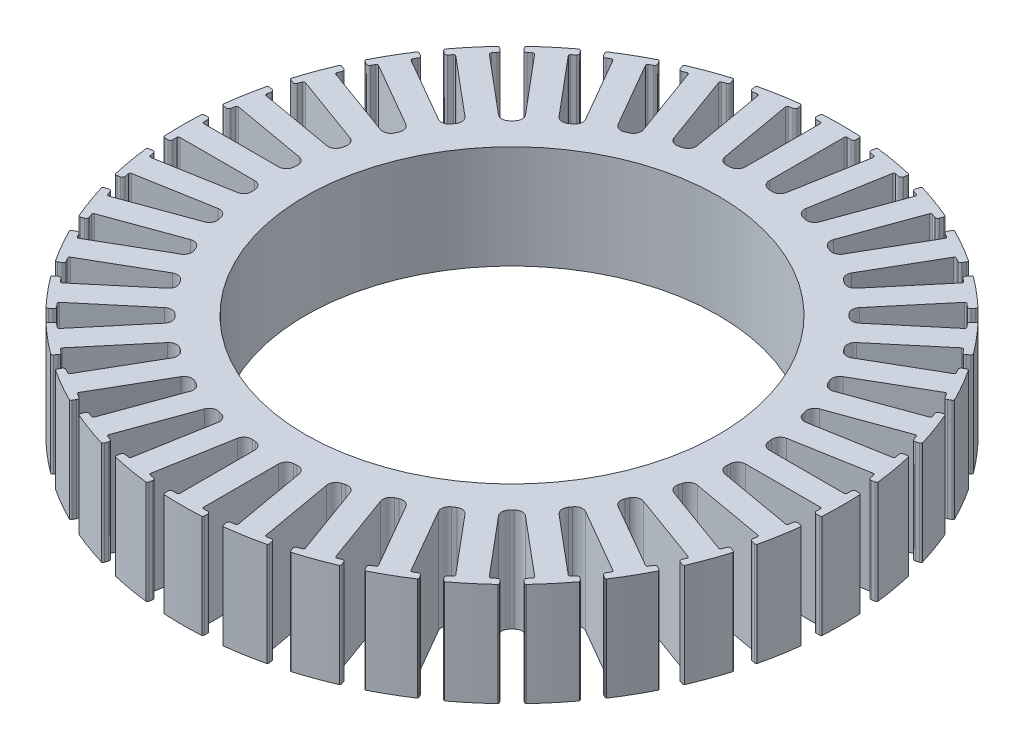
SolidWorks part; units mm, degrees
material "1023 Carbon Steel Sheet (SS)"
ref_plane "Front Plane" through (0, 0, 0) normal (0, 0, 1) x (1, 0, 0)
ref_plane "Top Plane" through (0, 0, 0) normal (0, 1, 0) x (1, 0, 0)
ref_plane "Right Plane" through (0, 0, 0) normal (1, 0, 0) x (0, 0, -1)
sketch "Sketch1" plane through (0, 0, 0) normal (0, 1, 0) x (1, 0, 0)
  line L0 (0, 0) -> (26, 0) construction
  line L1 (40.5, -1.7) -> (40.5, -2.2)
  line L2 (41.5, 1.5) -> (41.4729, 1.5)
  line L3 (41.5, 1.5) -> (41.5, -1.5)
  line L4 (41.5, -1.5) -> (41.4729, -1.5)
  line L6 (41.2, 2.5) -> (40.8, 2.5)
  line L7 (41.5, 2.2) -> (41.5, -2.2)
  line L8 (41.2, -2.5) -> (40.8, -2.5)
  line L9 (40.5, 2.2) -> (40.5, 1.7)
  line L10 (40.3, 1.5) -> (30.899, 1.5)
  line L11 (40.3, -1.5) -> (30.899, -1.5)
  line L12 (39.9482, -5.5208) -> (30.6901, -3.8883)
  line L13 (39.4273, -8.4752) -> (30.1691, -6.8428)
  line L14 (41.0082, -4.6923) -> (40.6143, -4.6228)
  line L15 (41.2515, -5.0398) -> (40.4875, -9.373)
  line L16 (40.2667, -4.8662) -> (40.1799, -5.3586)
  line L17 (39.5895, -8.7069) -> (39.5027, -9.1993)
  line L18 (40.14, -9.6163) -> (39.746, -9.5469)
  line L19 (38.3826, -12.3739) -> (29.5486, -9.1586)
  line L20 (37.3566, -15.193) -> (28.5226, -11.9776)
  line L21 (39.5704, -11.742) -> (39.1945, -11.6052)
  line L22 (39.7497, -12.1265) -> (38.2448, -16.2612)
  line L23 (38.81, -11.7845) -> (38.639, -12.2543)
  line L24 (37.4761, -15.4493) -> (37.3051, -15.9191)
  line L25 (37.8603, -16.4405) -> (37.4844, -16.3037)
  line L26 (35.6508, -18.851) -> (27.5093, -14.1505)
  line L27 (34.1508, -21.449) -> (26.0093, -16.7486)
  line L28 (36.9302, -18.4349) -> (36.5838, -18.2349)
  line L29 (37.0401, -18.8447) -> (34.8401, -22.6553)
  line L30 (36.174, -18.3447) -> (35.924, -18.7778)
  line L31 (34.224, -21.7222) -> (33.974, -22.1553)
  line L32 (34.4302, -22.7651) -> (34.0838, -22.5651)
  line L33 (31.8358, -24.7553) -> (24.6342, -18.7124)
  line L34 (29.9074, -27.0534) -> (22.7058, -21.0106)
  line L35 (33.168, -24.5677) -> (32.8616, -24.3106)
  line L36 (33.205, -24.9904) -> (30.3767, -28.361)
  line L37 (32.4389, -24.3476) -> (32.1175, -24.7306)
  line L38 (29.9321, -27.3352) -> (29.6107, -27.7182)
  line L39 (29.9541, -28.398) -> (29.6476, -28.1408)
  line L40 (27.0534, -29.9074) -> (21.0106, -22.7058)
  line L41 (24.7553, -31.8358) -> (18.7124, -24.6342)
  line L42 (28.398, -29.9541) -> (28.1408, -29.6476)
  line L43 (28.361, -30.3767) -> (24.9904, -33.205)
  line L44 (27.7182, -29.6107) -> (27.3352, -29.9321)
  line L45 (24.7306, -32.1175) -> (24.3476, -32.4389)
  line L46 (24.5677, -33.168) -> (24.3106, -32.8616)
  line L47 (21.449, -34.1508) -> (16.7486, -26.0093)
  line L48 (18.851, -35.6508) -> (14.1505, -27.5093)
  line L49 (22.7651, -34.4302) -> (22.5651, -34.0838)
  line L50 (22.6553, -34.8401) -> (18.8447, -37.0401)
  line L51 (22.1553, -33.974) -> (21.7222, -34.224)
  line L52 (18.7778, -35.924) -> (18.3447, -36.174)
  line L53 (18.4349, -36.9302) -> (18.2349, -36.5838)
  line L54 (11.9776, -28.5226) -> (15.193, -37.3566)
  line L55 (12.3739, -38.3826) -> (9.1586, -29.5486)
  line L56 (16.4405, -37.8603) -> (16.3037, -37.4844)
  line L57 (16.2612, -38.2448) -> (12.1265, -39.7497)
  line L58 (15.9191, -37.3051) -> (15.4493, -37.4761)
  line L59 (12.2543, -38.639) -> (11.7845, -38.81)
  line L60 (11.742, -39.5704) -> (11.6052, -39.1945)
  line L61 (8.4752, -39.4273) -> (6.8428, -30.1691)
  line L62 (5.5208, -39.9482) -> (3.8883, -30.6901)
  line L63 (9.6163, -40.14) -> (9.5469, -39.746)
  line L64 (9.373, -40.4875) -> (5.0398, -41.2515)
  line L65 (9.1993, -39.5027) -> (8.7069, -39.5895)
  line L66 (5.3586, -40.1799) -> (4.8662, -40.2667)
  line L67 (4.6923, -41.0082) -> (4.6228, -40.6143)
  line L68 (1.5, -40.3) -> (1.5, -30.899)
  line L69 (-1.5, -40.3) -> (-1.5, -30.899)
  line L70 (2.5, -41.2) -> (2.5, -40.8)
  line L71 (2.2, -41.5) -> (-2.2, -41.5)
  line L72 (2.2, -40.5) -> (1.7, -40.5)
  line L73 (-1.7, -40.5) -> (-2.2, -40.5)
  line L74 (-2.5, -41.2) -> (-2.5, -40.8)
  line L75 (-5.5208, -39.9482) -> (-3.8883, -30.6901)
  line L76 (-8.4752, -39.4273) -> (-6.8428, -30.1691)
  line L77 (-4.6923, -41.0082) -> (-4.6228, -40.6143)
  line L78 (-5.0398, -41.2515) -> (-9.373, -40.4875)
  line L79 (-4.8662, -40.2667) -> (-5.3586, -40.1799)
  line L80 (-8.7069, -39.5895) -> (-9.1993, -39.5027)
  line L81 (-9.6163, -40.14) -> (-9.5469, -39.746)
  line L82 (-12.3739, -38.3826) -> (-9.1586, -29.5486)
  line L83 (-15.193, -37.3566) -> (-11.9776, -28.5226)
  line L84 (-11.742, -39.5704) -> (-11.6052, -39.1945)
  line L85 (-12.1265, -39.7497) -> (-16.2612, -38.2448)
  line L86 (-11.7845, -38.81) -> (-12.2543, -38.639)
  line L87 (-15.4493, -37.4761) -> (-15.9191, -37.3051)
  line L88 (-16.4405, -37.8603) -> (-16.3037, -37.4844)
  line L89 (-18.851, -35.6508) -> (-14.1505, -27.5093)
  line L90 (-21.449, -34.1508) -> (-16.7486, -26.0093)
  line L91 (-18.4349, -36.9302) -> (-18.2349, -36.5838)
  line L92 (-18.8447, -37.0401) -> (-22.6553, -34.8401)
  line L93 (-18.3447, -36.174) -> (-18.7778, -35.924)
  line L94 (-21.7222, -34.224) -> (-22.1553, -33.974)
  line L95 (-22.7651, -34.4302) -> (-22.5651, -34.0838)
  line L96 (-24.7553, -31.8358) -> (-18.7124, -24.6342)
  line L97 (-27.0534, -29.9074) -> (-21.0106, -22.7058)
  line L98 (-24.5677, -33.168) -> (-24.3106, -32.8616)
  line L99 (-24.9904, -33.205) -> (-28.361, -30.3767)
  line L100 (-24.3476, -32.4389) -> (-24.7306, -32.1175)
  line L101 (-27.3352, -29.9321) -> (-27.7182, -29.6107)
  line L102 (-28.398, -29.9541) -> (-28.1408, -29.6476)
  line L103 (-29.9074, -27.0534) -> (-22.7058, -21.0106)
  line L104 (-31.8358, -24.7553) -> (-24.6342, -18.7124)
  line L105 (-29.9541, -28.398) -> (-29.6476, -28.1408)
  line L106 (-30.3767, -28.361) -> (-33.205, -24.9904)
  line L107 (-29.6107, -27.7182) -> (-29.9321, -27.3352)
  line L108 (-32.1175, -24.7306) -> (-32.4389, -24.3476)
  line L109 (-33.168, -24.5677) -> (-32.8616, -24.3106)
  line L110 (-34.1508, -21.449) -> (-26.0093, -16.7486)
  line L111 (-35.6508, -18.851) -> (-27.5093, -14.1505)
  line L112 (-34.4302, -22.7651) -> (-34.0838, -22.5651)
  line L113 (-34.8401, -22.6553) -> (-37.0401, -18.8447)
  line L114 (-33.974, -22.1553) -> (-34.224, -21.7222)
  line L115 (-35.924, -18.7778) -> (-36.174, -18.3447)
  line L116 (-36.9302, -18.4349) -> (-36.5838, -18.2349)
  line L117 (-37.3566, -15.193) -> (-28.5226, -11.9776)
  line L118 (-38.3826, -12.3739) -> (-29.5486, -9.1586)
  line L119 (-37.8603, -16.4405) -> (-37.4844, -16.3037)
  line L120 (-38.2448, -16.2612) -> (-39.7497, -12.1265)
  line L121 (-37.3051, -15.9191) -> (-37.4761, -15.4493)
  line L122 (-38.639, -12.2543) -> (-38.81, -11.7845)
  line L123 (-39.5704, -11.742) -> (-39.1945, -11.6052)
  line L124 (-39.4273, -8.4752) -> (-30.1691, -6.8428)
  line L125 (-39.9482, -5.5208) -> (-30.6901, -3.8883)
  line L126 (-40.14, -9.6163) -> (-39.746, -9.5469)
  line L127 (-40.4875, -9.373) -> (-41.2515, -5.0398)
  line L128 (-39.5027, -9.1993) -> (-39.5895, -8.7069)
  line L129 (-40.1799, -5.3586) -> (-40.2667, -4.8662)
  line L130 (-41.0082, -4.6923) -> (-40.6143, -4.6228)
  line L131 (-40.3, -1.5) -> (-30.899, -1.5)
  line L132 (-40.3, 1.5) -> (-30.899, 1.5)
  line L133 (-41.2, -2.5) -> (-40.8, -2.5)
  line L134 (-41.5, -2.2) -> (-41.5, 2.2)
  line L135 (-40.5, -2.2) -> (-40.5, -1.7)
  line L136 (-40.5, 1.7) -> (-40.5, 2.2)
  line L137 (-41.2, 2.5) -> (-40.8, 2.5)
  line L138 (-39.9482, 5.5208) -> (-30.6901, 3.8883)
  line L139 (-39.4273, 8.4752) -> (-30.1691, 6.8428)
  line L140 (-41.0082, 4.6923) -> (-40.6143, 4.6228)
  line L141 (-41.2515, 5.0398) -> (-40.4875, 9.373)
  line L142 (-40.2667, 4.8662) -> (-40.1799, 5.3586)
  line L143 (-39.5895, 8.7069) -> (-39.5027, 9.1993)
  line L144 (-40.14, 9.6163) -> (-39.746, 9.5469)
  line L145 (-38.3826, 12.3739) -> (-29.5486, 9.1586)
  line L146 (-37.3566, 15.193) -> (-28.5226, 11.9776)
  line L147 (-39.5704, 11.742) -> (-39.1945, 11.6052)
  line L148 (-39.7497, 12.1265) -> (-38.2448, 16.2612)
  line L149 (-38.81, 11.7845) -> (-38.639, 12.2543)
  line L150 (-37.4761, 15.4493) -> (-37.3051, 15.9191)
  line L151 (-37.8603, 16.4405) -> (-37.4844, 16.3037)
  line L152 (-35.6508, 18.851) -> (-27.5093, 14.1505)
  line L153 (-34.1508, 21.449) -> (-26.0093, 16.7486)
  line L154 (-36.9302, 18.4349) -> (-36.5838, 18.2349)
  line L155 (-37.0401, 18.8447) -> (-34.8401, 22.6553)
  line L156 (-36.174, 18.3447) -> (-35.924, 18.7778)
  line L157 (-34.224, 21.7222) -> (-33.974, 22.1553)
  line L158 (-34.4302, 22.7651) -> (-34.0838, 22.5651)
  line L159 (-31.8358, 24.7553) -> (-24.6342, 18.7124)
  line L160 (-29.9074, 27.0534) -> (-22.7058, 21.0106)
  line L161 (-33.168, 24.5677) -> (-32.8616, 24.3106)
  line L162 (-33.205, 24.9904) -> (-30.3767, 28.361)
  line L163 (-32.4389, 24.3476) -> (-32.1175, 24.7306)
  line L164 (-29.9321, 27.3352) -> (-29.6107, 27.7182)
  line L165 (-29.9541, 28.398) -> (-29.6476, 28.1408)
  line L166 (-27.0534, 29.9074) -> (-21.0106, 22.7058)
  line L167 (-24.7553, 31.8358) -> (-18.7124, 24.6342)
  line L168 (-28.398, 29.9541) -> (-28.1408, 29.6476)
  line L169 (-28.361, 30.3767) -> (-24.9904, 33.205)
  line L170 (-27.7182, 29.6107) -> (-27.3352, 29.9321)
  line L171 (-24.7306, 32.1175) -> (-24.3476, 32.4389)
  line L172 (-24.5677, 33.168) -> (-24.3106, 32.8616)
  line L173 (-21.449, 34.1508) -> (-16.7486, 26.0093)
  line L174 (-18.851, 35.6508) -> (-14.1505, 27.5093)
  line L175 (-22.7651, 34.4302) -> (-22.5651, 34.0838)
  line L176 (-22.6553, 34.8401) -> (-18.8447, 37.0401)
  line L177 (-22.1553, 33.974) -> (-21.7222, 34.224)
  line L178 (-18.7778, 35.924) -> (-18.3447, 36.174)
  line L179 (-18.4349, 36.9302) -> (-18.2349, 36.5838)
  line L180 (-15.193, 37.3566) -> (-11.9776, 28.5226)
  line L181 (-12.3739, 38.3826) -> (-9.1586, 29.5486)
  line L182 (-16.4405, 37.8603) -> (-16.3037, 37.4844)
  line L183 (-16.2612, 38.2448) -> (-12.1265, 39.7497)
  line L184 (-15.9191, 37.3051) -> (-15.4493, 37.4761)
  line L185 (-12.2543, 38.639) -> (-11.7845, 38.81)
  line L186 (-11.742, 39.5704) -> (-11.6052, 39.1945)
  line L187 (-8.4752, 39.4273) -> (-6.8428, 30.1691)
  line L188 (-5.5208, 39.9482) -> (-3.8883, 30.6901)
  line L189 (-9.6163, 40.14) -> (-9.5469, 39.746)
  line L190 (-9.373, 40.4875) -> (-5.0398, 41.2515)
  line L191 (-9.1993, 39.5027) -> (-8.7069, 39.5895)
  line L192 (-5.3586, 40.1799) -> (-4.8662, 40.2667)
  line L193 (-4.6923, 41.0082) -> (-4.6228, 40.6143)
  line L194 (-1.5, 40.3) -> (-1.5, 30.899)
  line L195 (1.5, 40.3) -> (1.5, 30.899)
  line L196 (-2.5, 41.2) -> (-2.5, 40.8)
  line L197 (-2.2, 41.5) -> (2.2, 41.5)
  line L198 (-2.2, 40.5) -> (-1.7, 40.5)
  line L199 (1.7, 40.5) -> (2.2, 40.5)
  line L200 (2.5, 41.2) -> (2.5, 40.8)
  line L201 (5.5208, 39.9482) -> (3.8883, 30.6901)
  line L202 (8.4752, 39.4273) -> (6.8428, 30.1691)
  line L203 (4.6923, 41.0082) -> (4.6228, 40.6143)
  line L204 (5.0398, 41.2515) -> (9.373, 40.4875)
  line L205 (4.8662, 40.2667) -> (5.3586, 40.1799)
  line L206 (8.7069, 39.5895) -> (9.1993, 39.5027)
  line L207 (9.6163, 40.14) -> (9.5469, 39.746)
  line L208 (12.3739, 38.3826) -> (9.1586, 29.5486)
  line L209 (15.193, 37.3566) -> (11.9776, 28.5226)
  line L210 (11.742, 39.5704) -> (11.6052, 39.1945)
  line L211 (12.1265, 39.7497) -> (16.2612, 38.2448)
  line L212 (11.7845, 38.81) -> (12.2543, 38.639)
  line L213 (15.4493, 37.4761) -> (15.9191, 37.3051)
  line L214 (16.4405, 37.8603) -> (16.3037, 37.4844)
  line L215 (18.851, 35.6508) -> (14.1505, 27.5093)
  line L216 (21.449, 34.1508) -> (16.7486, 26.0093)
  line L217 (18.4349, 36.9302) -> (18.2349, 36.5838)
  line L218 (18.8447, 37.0401) -> (22.6553, 34.8401)
  line L219 (18.3447, 36.174) -> (18.7778, 35.924)
  line L220 (21.7222, 34.224) -> (22.1553, 33.974)
  line L221 (22.7651, 34.4302) -> (22.5651, 34.0838)
  line L222 (24.7553, 31.8358) -> (18.7124, 24.6342)
  line L223 (27.0534, 29.9074) -> (21.0106, 22.7058)
  line L224 (24.5677, 33.168) -> (24.3106, 32.8616)
  line L225 (24.9904, 33.205) -> (28.361, 30.3767)
  line L226 (24.3476, 32.4389) -> (24.7306, 32.1175)
  line L227 (27.3352, 29.9321) -> (27.7182, 29.6107)
  line L228 (28.398, 29.9541) -> (28.1408, 29.6476)
  line L229 (29.9074, 27.0534) -> (22.7058, 21.0106)
  line L230 (31.8358, 24.7553) -> (24.6342, 18.7124)
  line L231 (29.9541, 28.398) -> (29.6476, 28.1408)
  line L232 (30.3767, 28.361) -> (33.205, 24.9904)
  line L233 (29.6107, 27.7182) -> (29.9321, 27.3352)
  line L234 (32.1175, 24.7306) -> (32.4389, 24.3476)
  line L235 (33.168, 24.5677) -> (32.8616, 24.3106)
  line L236 (34.1508, 21.449) -> (26.0093, 16.7486)
  line L237 (35.6508, 18.851) -> (27.5093, 14.1505)
  line L238 (34.4302, 22.7651) -> (34.0838, 22.5651)
  line L239 (34.8401, 22.6553) -> (37.0401, 18.8447)
  line L240 (33.974, 22.1553) -> (34.224, 21.7222)
  line L241 (35.924, 18.7778) -> (36.174, 18.3447)
  line L242 (36.9302, 18.4349) -> (36.5838, 18.2349)
  line L243 (37.3566, 15.193) -> (28.5226, 11.9776)
  line L244 (38.3826, 12.3739) -> (29.5486, 9.1586)
  line L245 (37.8603, 16.4405) -> (37.4844, 16.3037)
  line L246 (38.2448, 16.2612) -> (39.7497, 12.1265)
  line L247 (37.3051, 15.9191) -> (37.4761, 15.4493)
  line L248 (38.639, 12.2543) -> (38.81, 11.7845)
  line L249 (39.5704, 11.742) -> (39.1945, 11.6052)
  line L250 (39.4273, 8.4752) -> (30.1691, 6.8428)
  line L251 (39.9482, 5.5208) -> (30.6901, 3.8883)
  line L252 (40.14, 9.6163) -> (39.746, 9.5469)
  line L253 (40.4875, 9.373) -> (41.2515, 5.0398)
  line L254 (39.5027, 9.1993) -> (39.5895, 8.7069)
  line L255 (40.1799, 5.3586) -> (40.2667, 4.8662)
  line L256 (41.0082, 4.6923) -> (40.6143, 4.6228)
  line L257 (15.193, -37.3566) -> (11.9776, -28.5226) [skipped]
  line L258 (-7.5751, 29.0279) -> (-7.9537, 28.9291)
  line L259 (17.0464, -24.6865) -> (17.4841, -24.3842)
  circle A0 centre (0, 0) radius 41.5
  arc A1 (41.5, -2.2) -> (41.2, -2.5) centre (41.2, -2.2) cw
  arc A2 (40.8, -2.5) -> (40.5, -2.2) centre (40.8, -2.2) cw
  arc A3 (41.2, 2.5) -> (41.5, 2.2) centre (41.2, 2.2) cw
  arc A4 (40.8, 2.5) -> (40.5, 2.2) centre (40.8, 2.2) ccw
  arc A5 (40.5, -1.7) -> (40.3, -1.5) centre (40.3, -1.7) ccw
  arc A6 (40.5, 1.7) -> (40.3, 1.5) centre (40.3, 1.7) cw
  circle A7 centre (0, 0) radius 26
  arc A8 (29.9023, 2.4194) -> (29.8681, 2.8099) centre (0, 0) ccw
  arc A9 (30.899, -1.5) -> (29.9023, -2.4194) centre (30.899, -2.5) ccw
  arc A10 (30.899, 1.5) -> (29.9023, 2.4194) centre (30.899, 2.5) cw
  arc A11 (30.6901, -3.8883) -> (29.8681, -2.8099) centre (30.8637, -2.9035) cw
  arc A12 (30.1691, -6.8428) -> (29.0279, -7.5751) centre (29.9955, -7.8276) ccw
  arc A13 (41.0082, -4.6923) -> (41.2515, -5.0398) centre (40.9561, -4.9877) cw
  arc A14 (40.6143, -4.6228) -> (40.2667, -4.8662) centre (40.5622, -4.9183) ccw
  arc A15 (40.1799, -5.3586) -> (39.9482, -5.5208) centre (39.983, -5.3238) cw
  arc A16 (39.5895, -8.7069) -> (39.4273, -8.4752) centre (39.3926, -8.6722) ccw
  arc A17 (39.746, -9.5469) -> (39.5027, -9.1993) centre (39.7981, -9.2514) cw
  arc A18 (40.4875, -9.373) -> (40.14, -9.6163) centre (40.1921, -9.3209) cw
  arc A19 (29.5486, -9.1586) -> (28.9264, -7.9537) centre (29.8906, -8.2189) cw
  arc A20 (28.5226, -11.9776) -> (27.2715, -12.5006) centre (28.1805, -12.9173) ccw
  arc A21 (39.5704, -11.742) -> (39.7497, -12.1265) centre (39.4678, -12.0239) cw
  arc A22 (39.1945, -11.6052) -> (38.81, -11.7845) centre (39.0919, -11.8871) ccw
  arc A23 (38.639, -12.2543) -> (38.3826, -12.3739) centre (38.451, -12.1859) cw
  arc A24 (37.4761, -15.4493) -> (37.3566, -15.193) centre (37.2882, -15.3809) ccw
  arc A25 (37.4844, -16.3037) -> (37.3051, -15.9191) centre (37.587, -16.0217) cw
  arc A26 (38.2448, -16.2612) -> (37.8603, -16.4405) centre (37.9629, -16.1586) cw
  arc A27 (27.5093, -14.1505) -> (27.1058, -12.8559) centre (28.0093, -13.2845) cw
  arc A28 (26.0093, -16.7486) -> (24.6865, -17.0464) centre (25.5093, -17.6146) ccw
  arc A29 (36.9302, -18.4349) -> (37.0401, -18.8447) centre (36.7802, -18.6947) cw
  arc A30 (36.5838, -18.2349) -> (36.174, -18.3447) centre (36.4338, -18.4947) ccw
  arc A31 (35.924, -18.7778) -> (35.6508, -18.851) centre (35.7508, -18.6778) cw
  arc A32 (34.224, -21.7222) -> (34.1508, -21.449) centre (34.0508, -21.6222) ccw
  arc A33 (34.0838, -22.5651) -> (33.974, -22.1553) centre (34.2338, -22.3053) cw
  arc A34 (34.8401, -22.6553) -> (34.4302, -22.7651) centre (34.5802, -22.5053) cw
  arc A35 (24.6342, -18.7124) -> (24.4616, -17.3675) centre (25.277, -17.9464) cw
  arc A36 (22.7058, -21.0106) -> (21.3513, -21.0742) centre (22.0631, -21.7766) ccw
  arc A37 (33.168, -24.5677) -> (33.205, -24.9904) centre (32.9752, -24.7976) cw
  arc A38 (32.8616, -24.3106) -> (32.4389, -24.3476) centre (32.6687, -24.5404) ccw
  arc A39 (32.1175, -24.7306) -> (31.8358, -24.7553) centre (31.9643, -24.6021) cw
  arc A40 (29.9321, -27.3352) -> (29.9074, -27.0534) centre (29.7789, -27.2066) ccw
  arc A41 (29.6476, -28.1408) -> (29.6107, -27.7182) centre (29.8405, -27.911) cw
  arc A42 (30.3767, -28.361) -> (29.9541, -28.398) centre (30.1469, -28.1681) cw
  arc A43 (21.0106, -22.7058) -> (21.0742, -21.3513) centre (21.7766, -22.0631) cw
  arc A44 (-7.9537, 28.9291) -> (-9.1586, 29.5486) centre (-8.2197, 29.893) cw
  arc A45 (28.398, -29.9541) -> (28.361, -30.3767) centre (28.1681, -30.1469) cw
  arc A46 (28.1408, -29.6476) -> (27.7182, -29.6107) centre (27.911, -29.8405) ccw
  arc A47 (27.3352, -29.9321) -> (27.0534, -29.9074) centre (27.2066, -29.7789) cw
  arc A48 (24.7306, -32.1175) -> (24.7553, -31.8358) centre (24.6021, -31.9643) ccw
  arc A49 (24.3106, -32.8616) -> (24.3476, -32.4389) centre (24.5404, -32.6687) cw
  arc A50 (24.9904, -33.205) -> (24.5677, -33.168) centre (24.7976, -32.9752) cw
  arc A51 (16.7486, -26.0093) -> (17.0464, -24.6865) centre (17.6146, -25.5093) cw
  arc A52 (14.1505, -27.5093) -> (12.8559, -27.1058) centre (13.2845, -28.0093) ccw
  arc A53 (22.7651, -34.4302) -> (22.6553, -34.8401) centre (22.5053, -34.5802) cw
  arc A54 (22.5651, -34.0838) -> (22.1553, -33.974) centre (22.3053, -34.2338) ccw
  arc A55 (21.7222, -34.224) -> (21.449, -34.1508) centre (21.6222, -34.0508) cw
  arc A56 (18.7778, -35.924) -> (18.851, -35.6508) centre (18.6778, -35.7508) ccw
  arc A57 (18.2349, -36.5838) -> (18.3447, -36.174) centre (18.4947, -36.4338) cw
  arc A58 (18.8447, -37.0401) -> (18.4349, -36.9302) centre (18.6947, -36.7802) cw
  arc A59 (11.9776, -28.5226) -> (12.5006, -27.2715) centre (12.9173, -28.1805) cw
  arc A60 (9.1586, -29.5486) -> (7.9537, -28.9264) centre (8.2189, -29.8906) ccw
  arc A61 (16.4405, -37.8603) -> (16.2612, -38.2448) centre (16.1586, -37.9629) cw
  arc A62 (16.3037, -37.4844) -> (15.9191, -37.3051) centre (16.0217, -37.587) ccw
  arc A63 (15.4493, -37.4761) -> (15.193, -37.3566) centre (15.3809, -37.2882) cw
  arc A64 (12.2543, -38.639) -> (12.3739, -38.3826) centre (12.1859, -38.451) ccw
  arc A65 (11.6052, -39.1945) -> (11.7845, -38.81) centre (11.8871, -39.0919) cw
  arc A66 (12.1265, -39.7497) -> (11.742, -39.5704) centre (12.0239, -39.4678) cw
  arc A67 (6.8428, -30.1691) -> (7.5751, -29.0279) centre (7.8276, -29.9955) cw
  arc A68 (3.8883, -30.6901) -> (2.8099, -29.8681) centre (2.9035, -30.8637) ccw
  arc A69 (9.6163, -40.14) -> (9.373, -40.4875) centre (9.3209, -40.1921) cw
  arc A70 (9.5469, -39.746) -> (9.1993, -39.5027) centre (9.2514, -39.7981) ccw
  arc A71 (8.7069, -39.5895) -> (8.4752, -39.4273) centre (8.6722, -39.3926) cw
  arc A72 (5.3586, -40.1799) -> (5.5208, -39.9482) centre (5.3238, -39.983) ccw
  arc A73 (4.6228, -40.6143) -> (4.8662, -40.2667) centre (4.9183, -40.5622) cw
  arc A74 (5.0398, -41.2515) -> (4.6923, -41.0082) centre (4.9877, -40.9561) cw
  arc A75 (1.5, -30.899) -> (2.4194, -29.9023) centre (2.5, -30.899) cw
  arc A76 (-1.5, -30.899) -> (-2.4194, -29.9023) centre (-2.5, -30.899) ccw
  arc A77 (2.5, -41.2) -> (2.2, -41.5) centre (2.2, -41.2) cw
  arc A78 (2.5, -40.8) -> (2.2, -40.5) centre (2.2, -40.8) ccw
  arc A79 (1.7, -40.5) -> (1.5, -40.3) centre (1.7, -40.3) cw
  arc A80 (-1.7, -40.5) -> (-1.5, -40.3) centre (-1.7, -40.3) ccw
  arc A81 (-2.5, -40.8) -> (-2.2, -40.5) centre (-2.2, -40.8) cw
  arc A82 (-2.2, -41.5) -> (-2.5, -41.2) centre (-2.2, -41.2) cw
  arc A83 (-3.8883, -30.6901) -> (-2.8099, -29.8681) centre (-2.9035, -30.8637) cw
  arc A84 (-6.8428, -30.1691) -> (-7.5751, -29.0279) centre (-7.8276, -29.9955) ccw
  arc A85 (-4.6923, -41.0082) -> (-5.0398, -41.2515) centre (-4.9877, -40.9561) cw
  arc A86 (-4.6228, -40.6143) -> (-4.8662, -40.2667) centre (-4.9183, -40.5622) ccw
  arc A87 (-5.3586, -40.1799) -> (-5.5208, -39.9482) centre (-5.3238, -39.983) cw
  arc A88 (-8.7069, -39.5895) -> (-8.4752, -39.4273) centre (-8.6722, -39.3926) ccw
  arc A89 (-9.5469, -39.746) -> (-9.1993, -39.5027) centre (-9.2514, -39.7981) cw
  arc A90 (-9.373, -40.4875) -> (-9.6163, -40.14) centre (-9.3209, -40.1921) cw
  arc A91 (-9.1586, -29.5486) -> (-7.9537, -28.9264) centre (-8.2189, -29.8906) cw
  arc A92 (-11.9776, -28.5226) -> (-12.5006, -27.2715) centre (-12.9173, -28.1805) ccw
  arc A93 (-11.742, -39.5704) -> (-12.1265, -39.7497) centre (-12.0239, -39.4678) cw
  arc A94 (-11.6052, -39.1945) -> (-11.7845, -38.81) centre (-11.8871, -39.0919) ccw
  arc A95 (-12.2543, -38.639) -> (-12.3739, -38.3826) centre (-12.1859, -38.451) cw
  arc A96 (-15.4493, -37.4761) -> (-15.193, -37.3566) centre (-15.3809, -37.2882) ccw
  arc A97 (-16.3037, -37.4844) -> (-15.9191, -37.3051) centre (-16.0217, -37.587) cw
  arc A98 (-16.2612, -38.2448) -> (-16.4405, -37.8603) centre (-16.1586, -37.9629) cw
  arc A99 (-14.1505, -27.5093) -> (-12.8559, -27.1058) centre (-13.2845, -28.0093) cw
  arc A100 (-16.7486, -26.0093) -> (-17.0464, -24.6865) centre (-17.6146, -25.5093) ccw
  arc A101 (-18.4349, -36.9302) -> (-18.8447, -37.0401) centre (-18.6947, -36.7802) cw
  arc A102 (-18.2349, -36.5838) -> (-18.3447, -36.174) centre (-18.4947, -36.4338) ccw
  arc A103 (-18.7778, -35.924) -> (-18.851, -35.6508) centre (-18.6778, -35.7508) cw
  arc A104 (-21.7222, -34.224) -> (-21.449, -34.1508) centre (-21.6222, -34.0508) ccw
  arc A105 (-22.5651, -34.0838) -> (-22.1553, -33.974) centre (-22.3053, -34.2338) cw
  arc A106 (-22.6553, -34.8401) -> (-22.7651, -34.4302) centre (-22.5053, -34.5802) cw
  arc A107 (-18.7124, -24.6342) -> (-17.3675, -24.4616) centre (-17.9464, -25.277) cw
  arc A108 (-21.0106, -22.7058) -> (-21.0742, -21.3513) centre (-21.7766, -22.0631) ccw
  arc A109 (-24.5677, -33.168) -> (-24.9904, -33.205) centre (-24.7976, -32.9752) cw
  arc A110 (-24.3106, -32.8616) -> (-24.3476, -32.4389) centre (-24.5404, -32.6687) ccw
  arc A111 (-24.7306, -32.1175) -> (-24.7553, -31.8358) centre (-24.6021, -31.9643) cw
  arc A112 (-27.3352, -29.9321) -> (-27.0534, -29.9074) centre (-27.2066, -29.7789) ccw
  arc A113 (-28.1408, -29.6476) -> (-27.7182, -29.6107) centre (-27.911, -29.8405) cw
  arc A114 (-28.361, -30.3767) -> (-28.398, -29.9541) centre (-28.1681, -30.1469) cw
  arc A115 (-22.7058, -21.0106) -> (-21.3513, -21.0742) centre (-22.0631, -21.7766) cw
  arc A116 (-24.6342, -18.7124) -> (-24.4616, -17.3675) centre (-25.277, -17.9464) ccw
  arc A117 (-29.9541, -28.398) -> (-30.3767, -28.361) centre (-30.1469, -28.1681) cw
  arc A118 (-29.6476, -28.1408) -> (-29.6107, -27.7182) centre (-29.8405, -27.911) ccw
  arc A119 (-29.9321, -27.3352) -> (-29.9074, -27.0534) centre (-29.7789, -27.2066) cw
  arc A120 (-32.1175, -24.7306) -> (-31.8358, -24.7553) centre (-31.9643, -24.6021) ccw
  arc A121 (-32.8616, -24.3106) -> (-32.4389, -24.3476) centre (-32.6687, -24.5404) cw
  arc A122 (-33.205, -24.9904) -> (-33.168, -24.5677) centre (-32.9752, -24.7976) cw
  arc A123 (-26.0093, -16.7486) -> (-24.6865, -17.0464) centre (-25.5093, -17.6146) cw
  arc A124 (-27.5093, -14.1505) -> (-27.1058, -12.8559) centre (-28.0093, -13.2845) ccw
  arc A125 (-34.4302, -22.7651) -> (-34.8401, -22.6553) centre (-34.5802, -22.5053) cw
  arc A126 (-34.0838, -22.5651) -> (-33.974, -22.1553) centre (-34.2338, -22.3053) ccw
  arc A127 (-34.224, -21.7222) -> (-34.1508, -21.449) centre (-34.0508, -21.6222) cw
  arc A128 (-35.924, -18.7778) -> (-35.6508, -18.851) centre (-35.7508, -18.6778) ccw
  arc A129 (-36.5838, -18.2349) -> (-36.174, -18.3447) centre (-36.4338, -18.4947) cw
  arc A130 (-37.0401, -18.8447) -> (-36.9302, -18.4349) centre (-36.7802, -18.6947) cw
  arc A131 (-28.5226, -11.9776) -> (-27.2715, -12.5006) centre (-28.1805, -12.9173) cw
  arc A132 (-29.5486, -9.1586) -> (-28.9264, -7.9537) centre (-29.8906, -8.2189) ccw
  arc A133 (-37.8603, -16.4405) -> (-38.2448, -16.2612) centre (-37.9629, -16.1586) cw
  arc A134 (-37.4844, -16.3037) -> (-37.3051, -15.9191) centre (-37.587, -16.0217) ccw
  arc A135 (-37.4761, -15.4493) -> (-37.3566, -15.193) centre (-37.2882, -15.3809) cw
  arc A136 (-38.639, -12.2543) -> (-38.3826, -12.3739) centre (-38.451, -12.1859) ccw
  arc A137 (-39.1945, -11.6052) -> (-38.81, -11.7845) centre (-39.0919, -11.8871) cw
  arc A138 (-39.7497, -12.1265) -> (-39.5704, -11.742) centre (-39.4678, -12.0239) cw
  arc A139 (-30.1691, -6.8428) -> (-29.0279, -7.5751) centre (-29.9955, -7.8276) cw
  arc A140 (-30.6901, -3.8883) -> (-29.8681, -2.8099) centre (-30.8637, -2.9035) ccw
  arc A141 (-40.14, -9.6163) -> (-40.4875, -9.373) centre (-40.1921, -9.3209) cw
  arc A142 (-39.746, -9.5469) -> (-39.5027, -9.1993) centre (-39.7981, -9.2514) ccw
  arc A143 (-39.5895, -8.7069) -> (-39.4273, -8.4752) centre (-39.3926, -8.6722) cw
  arc A144 (-40.1799, -5.3586) -> (-39.9482, -5.5208) centre (-39.983, -5.3238) ccw
  arc A145 (-40.6143, -4.6228) -> (-40.2667, -4.8662) centre (-40.5622, -4.9183) cw
  arc A146 (-41.2515, -5.0398) -> (-41.0082, -4.6923) centre (-40.9561, -4.9877) cw
  arc A147 (-30.899, -1.5) -> (-29.9023, -2.4194) centre (-30.899, -2.5) cw
  arc A148 (-30.899, 1.5) -> (-29.9023, 2.4194) centre (-30.899, 2.5) ccw
  arc A149 (-41.2, -2.5) -> (-41.5, -2.2) centre (-41.2, -2.2) cw
  arc A150 (-40.8, -2.5) -> (-40.5, -2.2) centre (-40.8, -2.2) ccw
  arc A151 (-40.5, -1.7) -> (-40.3, -1.5) centre (-40.3, -1.7) cw
  arc A152 (-40.5, 1.7) -> (-40.3, 1.5) centre (-40.3, 1.7) ccw
  arc A153 (-40.8, 2.5) -> (-40.5, 2.2) centre (-40.8, 2.2) cw
  arc A154 (-41.5, 2.2) -> (-41.2, 2.5) centre (-41.2, 2.2) cw
  arc A155 (-30.6901, 3.8883) -> (-29.8681, 2.8099) centre (-30.8637, 2.9035) cw
  arc A156 (-30.1691, 6.8428) -> (-29.0279, 7.5751) centre (-29.9955, 7.8276) ccw
  arc A157 (-41.0082, 4.6923) -> (-41.2515, 5.0398) centre (-40.9561, 4.9877) cw
  arc A158 (-40.6143, 4.6228) -> (-40.2667, 4.8662) centre (-40.5622, 4.9183) ccw
  arc A159 (-40.1799, 5.3586) -> (-39.9482, 5.5208) centre (-39.983, 5.3238) cw
  arc A160 (-39.5895, 8.7069) -> (-39.4273, 8.4752) centre (-39.3926, 8.6722) ccw
  arc A161 (-39.746, 9.5469) -> (-39.5027, 9.1993) centre (-39.7981, 9.2514) cw
  arc A162 (-40.4875, 9.373) -> (-40.14, 9.6163) centre (-40.1921, 9.3209) cw
  arc A163 (-29.5486, 9.1586) -> (-28.9264, 7.9537) centre (-29.8906, 8.2189) cw
  arc A164 (-28.5226, 11.9776) -> (-27.2715, 12.5006) centre (-28.1805, 12.9173) ccw
  arc A165 (-39.5704, 11.742) -> (-39.7497, 12.1265) centre (-39.4678, 12.0239) cw
  arc A166 (-39.1945, 11.6052) -> (-38.81, 11.7845) centre (-39.0919, 11.8871) ccw
  arc A167 (-38.639, 12.2543) -> (-38.3826, 12.3739) centre (-38.451, 12.1859) cw
  arc A168 (-37.4761, 15.4493) -> (-37.3566, 15.193) centre (-37.2882, 15.3809) ccw
  arc A169 (-37.4844, 16.3037) -> (-37.3051, 15.9191) centre (-37.587, 16.0217) cw
  arc A170 (-38.2448, 16.2612) -> (-37.8603, 16.4405) centre (-37.9629, 16.1586) cw
  arc A171 (-27.5093, 14.1505) -> (-27.1058, 12.8559) centre (-28.0093, 13.2845) cw
  arc A172 (-26.0093, 16.7486) -> (-24.6865, 17.0464) centre (-25.5093, 17.6146) ccw
  arc A173 (-36.9302, 18.4349) -> (-37.0401, 18.8447) centre (-36.7802, 18.6947) cw
  arc A174 (-36.5838, 18.2349) -> (-36.174, 18.3447) centre (-36.4338, 18.4947) ccw
  arc A175 (-35.924, 18.7778) -> (-35.6508, 18.851) centre (-35.7508, 18.6778) cw
  arc A176 (-34.224, 21.7222) -> (-34.1508, 21.449) centre (-34.0508, 21.6222) ccw
  arc A177 (-34.0838, 22.5651) -> (-33.974, 22.1553) centre (-34.2338, 22.3053) cw
  arc A178 (-34.8401, 22.6553) -> (-34.4302, 22.7651) centre (-34.5802, 22.5053) cw
  arc A179 (-24.6342, 18.7124) -> (-24.4616, 17.3675) centre (-25.277, 17.9464) cw
  arc A180 (-22.7058, 21.0106) -> (-21.3513, 21.0742) centre (-22.0631, 21.7766) ccw
  arc A181 (-33.168, 24.5677) -> (-33.205, 24.9904) centre (-32.9752, 24.7976) cw
  arc A182 (-32.8616, 24.3106) -> (-32.4389, 24.3476) centre (-32.6687, 24.5404) ccw
  arc A183 (-32.1175, 24.7306) -> (-31.8358, 24.7553) centre (-31.9643, 24.6021) cw
  arc A184 (-29.9321, 27.3352) -> (-29.9074, 27.0534) centre (-29.7789, 27.2066) ccw
  arc A185 (-29.6476, 28.1408) -> (-29.6107, 27.7182) centre (-29.8405, 27.911) cw
  arc A186 (-30.3767, 28.361) -> (-29.9541, 28.398) centre (-30.1469, 28.1681) cw
  arc A187 (-21.0106, 22.7058) -> (-21.0742, 21.3513) centre (-21.7766, 22.0631) cw
  arc A188 (-18.7124, 24.6342) -> (-17.3675, 24.4616) centre (-17.9464, 25.277) ccw
  arc A189 (-28.398, 29.9541) -> (-28.361, 30.3767) centre (-28.1681, 30.1469) cw
  arc A190 (-28.1408, 29.6476) -> (-27.7182, 29.6107) centre (-27.911, 29.8405) ccw
  arc A191 (-27.3352, 29.9321) -> (-27.0534, 29.9074) centre (-27.2066, 29.7789) cw
  arc A192 (-24.7306, 32.1175) -> (-24.7553, 31.8358) centre (-24.6021, 31.9643) ccw
  arc A193 (-24.3106, 32.8616) -> (-24.3476, 32.4389) centre (-24.5404, 32.6687) cw
  arc A194 (-24.9904, 33.205) -> (-24.5677, 33.168) centre (-24.7976, 32.9752) cw
  arc A195 (-16.7486, 26.0093) -> (-17.0464, 24.6865) centre (-17.6146, 25.5093) cw
  arc A196 (-14.1505, 27.5093) -> (-12.8559, 27.1058) centre (-13.2845, 28.0093) ccw
  arc A197 (-22.7651, 34.4302) -> (-22.6553, 34.8401) centre (-22.5053, 34.5802) cw
  arc A198 (-22.5651, 34.0838) -> (-22.1553, 33.974) centre (-22.3053, 34.2338) ccw
  arc A199 (-21.7222, 34.224) -> (-21.449, 34.1508) centre (-21.6222, 34.0508) cw
  arc A200 (-18.7778, 35.924) -> (-18.851, 35.6508) centre (-18.6778, 35.7508) ccw
  arc A201 (-18.2349, 36.5838) -> (-18.3447, 36.174) centre (-18.4947, 36.4338) cw
  arc A202 (-18.8447, 37.0401) -> (-18.4349, 36.9302) centre (-18.6947, 36.7802) cw
  arc A203 (-11.9776, 28.5226) -> (-12.5006, 27.2715) centre (-12.9173, 28.1805) cw
  arc A204 (17.4841, -24.3842) -> (18.7124, -24.6342) centre (17.9429, -25.2728) cw
  arc A205 (-16.4405, 37.8603) -> (-16.2612, 38.2448) centre (-16.1586, 37.9629) cw
  arc A206 (-16.3037, 37.4844) -> (-15.9191, 37.3051) centre (-16.0217, 37.587) ccw
  arc A207 (-15.4493, 37.4761) -> (-15.193, 37.3566) centre (-15.3809, 37.2882) cw
  arc A208 (-12.2543, 38.639) -> (-12.3739, 38.3826) centre (-12.1859, 38.451) ccw
  arc A209 (-11.6052, 39.1945) -> (-11.7845, 38.81) centre (-11.8871, 39.0919) cw
  arc A210 (-12.1265, 39.7497) -> (-11.742, 39.5704) centre (-12.0239, 39.4678) cw
  arc A211 (-6.8428, 30.1691) -> (-7.5751, 29.0279) centre (-7.8276, 29.9955) cw
  arc A212 (-3.8883, 30.6901) -> (-2.8099, 29.8681) centre (-2.9035, 30.8637) ccw
  arc A213 (-9.6163, 40.14) -> (-9.373, 40.4875) centre (-9.3209, 40.1921) cw
  arc A214 (-9.5469, 39.746) -> (-9.1993, 39.5027) centre (-9.2514, 39.7981) ccw
  arc A215 (-8.7069, 39.5895) -> (-8.4752, 39.4273) centre (-8.6722, 39.3926) cw
  arc A216 (-5.3586, 40.1799) -> (-5.5208, 39.9482) centre (-5.3238, 39.983) ccw
  arc A217 (-4.6228, 40.6143) -> (-4.8662, 40.2667) centre (-4.9183, 40.5622) cw
  arc A218 (-5.0398, 41.2515) -> (-4.6923, 41.0082) centre (-4.9877, 40.9561) cw
  arc A219 (-1.5, 30.899) -> (-2.4194, 29.9023) centre (-2.5, 30.899) cw
  arc A220 (1.5, 30.899) -> (2.4194, 29.9023) centre (2.5, 30.899) ccw
  arc A221 (-2.5, 41.2) -> (-2.2, 41.5) centre (-2.2, 41.2) cw
  arc A222 (-2.5, 40.8) -> (-2.2, 40.5) centre (-2.2, 40.8) ccw
  arc A223 (-1.7, 40.5) -> (-1.5, 40.3) centre (-1.7, 40.3) cw
  arc A224 (1.7, 40.5) -> (1.5, 40.3) centre (1.7, 40.3) ccw
  arc A225 (2.5, 40.8) -> (2.2, 40.5) centre (2.2, 40.8) cw
  arc A226 (2.2, 41.5) -> (2.5, 41.2) centre (2.2, 41.2) cw
  arc A227 (3.8883, 30.6901) -> (2.8099, 29.8681) centre (2.9035, 30.8637) cw
  arc A228 (6.8428, 30.1691) -> (7.5751, 29.0279) centre (7.8276, 29.9955) ccw
  arc A229 (4.6923, 41.0082) -> (5.0398, 41.2515) centre (4.9877, 40.9561) cw
  arc A230 (4.6228, 40.6143) -> (4.8662, 40.2667) centre (4.9183, 40.5622) ccw
  arc A231 (5.3586, 40.1799) -> (5.5208, 39.9482) centre (5.3238, 39.983) cw
  arc A232 (8.7069, 39.5895) -> (8.4752, 39.4273) centre (8.6722, 39.3926) ccw
  arc A233 (9.5469, 39.746) -> (9.1993, 39.5027) centre (9.2514, 39.7981) cw
  arc A234 (9.373, 40.4875) -> (9.6163, 40.14) centre (9.3209, 40.1921) cw
  arc A235 (9.1586, 29.5486) -> (7.9537, 28.9264) centre (8.2189, 29.8906) cw
  arc A236 (11.9776, 28.5226) -> (12.5006, 27.2715) centre (12.9173, 28.1805) ccw
  arc A237 (11.742, 39.5704) -> (12.1265, 39.7497) centre (12.0239, 39.4678) cw
  arc A238 (11.6052, 39.1945) -> (11.7845, 38.81) centre (11.8871, 39.0919) ccw
  arc A239 (12.2543, 38.639) -> (12.3739, 38.3826) centre (12.1859, 38.451) cw
  arc A240 (15.4493, 37.4761) -> (15.193, 37.3566) centre (15.3809, 37.2882) ccw
  arc A241 (16.3037, 37.4844) -> (15.9191, 37.3051) centre (16.0217, 37.587) cw
  arc A242 (16.2612, 38.2448) -> (16.4405, 37.8603) centre (16.1586, 37.9629) cw
  arc A243 (14.1505, 27.5093) -> (12.8559, 27.1058) centre (13.2845, 28.0093) cw
  arc A244 (16.7486, 26.0093) -> (17.0464, 24.6865) centre (17.6146, 25.5093) ccw
  arc A245 (18.4349, 36.9302) -> (18.8447, 37.0401) centre (18.6947, 36.7802) cw
  arc A246 (18.2349, 36.5838) -> (18.3447, 36.174) centre (18.4947, 36.4338) ccw
  arc A247 (18.7778, 35.924) -> (18.851, 35.6508) centre (18.6778, 35.7508) cw
  arc A248 (21.7222, 34.224) -> (21.449, 34.1508) centre (21.6222, 34.0508) ccw
  arc A249 (22.5651, 34.0838) -> (22.1553, 33.974) centre (22.3053, 34.2338) cw
  arc A250 (22.6553, 34.8401) -> (22.7651, 34.4302) centre (22.5053, 34.5802) cw
  arc A251 (18.7124, 24.6342) -> (17.3675, 24.4616) centre (17.9464, 25.277) cw
  arc A252 (21.0106, 22.7058) -> (21.0742, 21.3513) centre (21.7766, 22.0631) ccw
  arc A253 (24.5677, 33.168) -> (24.9904, 33.205) centre (24.7976, 32.9752) cw
  arc A254 (24.3106, 32.8616) -> (24.3476, 32.4389) centre (24.5404, 32.6687) ccw
  arc A255 (24.7306, 32.1175) -> (24.7553, 31.8358) centre (24.6021, 31.9643) cw
  arc A256 (27.3352, 29.9321) -> (27.0534, 29.9074) centre (27.2066, 29.7789) ccw
  arc A257 (28.1408, 29.6476) -> (27.7182, 29.6107) centre (27.911, 29.8405) cw
  arc A258 (28.361, 30.3767) -> (28.398, 29.9541) centre (28.1681, 30.1469) cw
  arc A259 (22.7058, 21.0106) -> (21.3513, 21.0742) centre (22.0631, 21.7766) cw
  arc A260 (24.6342, 18.7124) -> (24.4616, 17.3675) centre (25.277, 17.9464) ccw
  arc A261 (29.9541, 28.398) -> (30.3767, 28.361) centre (30.1469, 28.1681) cw
  arc A262 (29.6476, 28.1408) -> (29.6107, 27.7182) centre (29.8405, 27.911) ccw
  arc A263 (29.9321, 27.3352) -> (29.9074, 27.0534) centre (29.7789, 27.2066) cw
  arc A264 (32.1175, 24.7306) -> (31.8358, 24.7553) centre (31.9643, 24.6021) ccw
  arc A265 (32.8616, 24.3106) -> (32.4389, 24.3476) centre (32.6687, 24.5404) cw
  arc A266 (33.205, 24.9904) -> (33.168, 24.5677) centre (32.9752, 24.7976) cw
  arc A267 (26.0093, 16.7486) -> (24.6865, 17.0464) centre (25.5093, 17.6146) cw
  arc A268 (27.5093, 14.1505) -> (27.1058, 12.8559) centre (28.0093, 13.2845) ccw
  arc A269 (34.4302, 22.7651) -> (34.8401, 22.6553) centre (34.5802, 22.5053) cw
  arc A270 (34.0838, 22.5651) -> (33.974, 22.1553) centre (34.2338, 22.3053) ccw
  arc A271 (34.224, 21.7222) -> (34.1508, 21.449) centre (34.0508, 21.6222) cw
  arc A272 (35.924, 18.7778) -> (35.6508, 18.851) centre (35.7508, 18.6778) ccw
  arc A273 (36.5838, 18.2349) -> (36.174, 18.3447) centre (36.4338, 18.4947) cw
  arc A274 (37.0401, 18.8447) -> (36.9302, 18.4349) centre (36.7802, 18.6947) cw
  arc A275 (28.5226, 11.9776) -> (27.2715, 12.5006) centre (28.1805, 12.9173) cw
  arc A276 (29.5486, 9.1586) -> (28.9264, 7.9537) centre (29.8906, 8.2189) ccw
  arc A277 (37.8603, 16.4405) -> (38.2448, 16.2612) centre (37.9629, 16.1586) cw
  arc A278 (37.4844, 16.3037) -> (37.3051, 15.9191) centre (37.587, 16.0217) ccw
  arc A279 (37.4761, 15.4493) -> (37.3566, 15.193) centre (37.2882, 15.3809) cw
  arc A280 (38.639, 12.2543) -> (38.3826, 12.3739) centre (38.451, 12.1859) ccw
  arc A281 (39.1945, 11.6052) -> (38.81, 11.7845) centre (39.0919, 11.8871) cw
  arc A282 (39.7497, 12.1265) -> (39.5704, 11.742) centre (39.4678, 12.0239) cw
  arc A283 (30.1691, 6.8428) -> (29.0279, 7.5751) centre (29.9955, 7.8276) cw
  arc A284 (30.6901, 3.8883) -> (29.8681, 2.8099) centre (30.8637, 2.9035) ccw
  arc A285 (40.14, 9.6163) -> (40.4875, 9.373) centre (40.1921, 9.3209) cw
  arc A286 (39.746, 9.5469) -> (39.5027, 9.1993) centre (39.7981, 9.2514) ccw
  arc A287 (39.5895, 8.7069) -> (39.4273, 8.4752) centre (39.3926, 8.6722) cw
  arc A288 (40.1799, 5.3586) -> (39.9482, 5.5208) centre (39.983, 5.3238) ccw
  arc A289 (40.6143, 4.6228) -> (40.2667, 4.8662) centre (40.5622, 4.9183) cw
  arc A290 (41.2515, 5.0398) -> (41.0082, 4.6923) centre (40.9561, 4.9877) cw
  arc A291 (-28.9264, 7.9537) -> (-29.0279, 7.5751) centre (0, 0) ccw
  arc A292 (-27.1058, 12.8559) -> (-27.2715, 12.5006) centre (0, 0) ccw
  arc A293 (-24.4616, 17.3675) -> (-24.6865, 17.0464) centre (0, 0) ccw
  arc A294 (-21.0742, 21.3513) -> (-21.3513, 21.0742) centre (0, 0) ccw
  arc A295 (-29.8681, 2.8099) -> (-29.9023, 2.4194) centre (0, 0) ccw
  arc A296 (-29.9023, -2.4194) -> (-29.8681, -2.8099) centre (0, 0) ccw
  arc A297 (-29.0279, -7.5751) -> (-28.9264, -7.9537) centre (0, 0) ccw
  arc A298 (-27.2715, -12.5006) -> (-27.1058, -12.8559) centre (0, 0) ccw
  arc A299 (-24.6865, -17.0464) -> (-24.4616, -17.3675) centre (0, 0) ccw
  arc A300 (-21.3513, -21.0742) -> (-21.0742, -21.3513) centre (0, 0) ccw
  arc A301 (-17.3675, -24.4616) -> (-17.0464, -24.6865) centre (0, 0) ccw
  arc A302 (-12.8559, -27.1058) -> (-12.5006, -27.2715) centre (0, 0) ccw
  arc A303 (-7.9537, -28.9264) -> (-7.5751, -29.0279) centre (0, 0) ccw
  arc A304 (-2.8099, -29.8681) -> (-2.4194, -29.9023) centre (0, 0) ccw
  arc A305 (2.4194, -29.9023) -> (2.8099, -29.8681) centre (0, 0) ccw
  arc A306 (7.5751, -29.0279) -> (7.9537, -28.9264) centre (0, 0) ccw
  arc A307 (12.5006, -27.2715) -> (12.8559, -27.1058) centre (0, 0) ccw
  arc A308 (21.0742, -21.3513) -> (21.3513, -21.0742) centre (0, 0) ccw
  arc A309 (18.7124, -24.6342) -> (17.3675, -24.4616) centre (17.9464, -25.277) ccw [skipped]
  arc A310 (24.4616, -17.3675) -> (24.6865, -17.0464) centre (0, 0) ccw
  arc A311 (27.1058, -12.8559) -> (27.2715, -12.5006) centre (0, 0) ccw
  arc A312 (28.9264, -7.9537) -> (29.0279, -7.5751) centre (0, 0) ccw
  arc A313 (29.8681, -2.8099) -> (29.9023, -2.4194) centre (0, 0) ccw
  arc A314 (29.0279, 7.5751) -> (28.9264, 7.9537) centre (0, 0) ccw
  arc A315 (27.2715, 12.5006) -> (27.1058, 12.8559) centre (0, 0) ccw
  arc A316 (24.6865, 17.0464) -> (24.4616, 17.3675) centre (0, 0) ccw
  arc A317 (21.3513, 21.0742) -> (21.0742, 21.3513) centre (0, 0) ccw
  arc A318 (17.3675, 24.4616) -> (17.0464, 24.6865) centre (0, 0) ccw
  arc A319 (12.8559, 27.1058) -> (12.5006, 27.2715) centre (0, 0) ccw
  arc A320 (7.9537, 28.9264) -> (7.5751, 29.0279) centre (0, 0) ccw
  arc A321 (2.8099, 29.8681) -> (2.4194, 29.9023) centre (0, 0) ccw
  arc A322 (-2.4194, 29.9023) -> (-2.8099, 29.8681) centre (0, 0) ccw
  arc A323 (-12.5006, 27.2715) -> (-12.8559, 27.1058) centre (0, 0) ccw
  arc A324 (-9.1586, 29.5486) -> (-7.9537, 28.9264) centre (-8.2189, 29.8906) ccw [skipped]
  arc A325 (-17.0464, 24.6865) -> (-17.3675, 24.4616) centre (0, 0) ccw
  point P8 (41.5, 0)
  point P16 (41.5, -2.5)
  point P21 (41.5, 2.5)
  point P24 (40.5, 2.5)
  point P30 (40.5, -1.5)
  point P33 (40.5, 1.5)
  point P882 (0, 0)
  dimension "D1" = 83
  dimension "D8" = 0.3
  dimension "D6" = 0.2
  dimension "D9" = 52
  dimension "D10" = 60
  dimension "D2" = 1
  dimension "D4" = 1
  dimension "D12" = 1
  dimension "D3" = 0
  dimension "D5" = 5
  dimension "D7" = 1
  dimension "D11" = 36
extrude "Boss-Extrude1" add sketch "Sketch1" along normal blind 13 contours A195 A325 A188 L167 A192 L171 A193 L172 A194 A0 A189 L168 A190 L170 A191 L166 A187 A294 A180 L160 A184 L164 A185 L165 A186 A181 L161 A182 L163 A183 L159 A179 A293 A172 L153 A176 L157 A177 L158 A178 A173 L154 A174 L156 A175 L152 region at (41.2714, 0, 0.7286)
